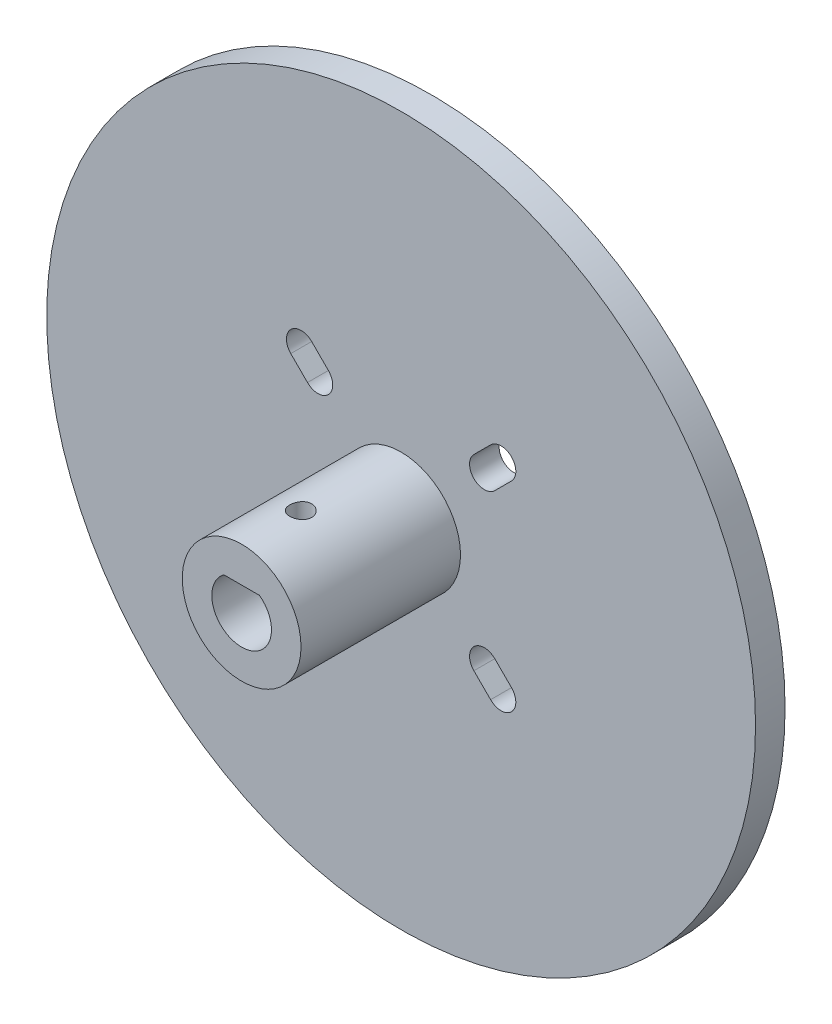
SolidWorks part; units mm, degrees
ref_plane "Front Plane" through (0, 0, 0) normal (0, 0, 1) x (1, 0, 0)
ref_plane "Top Plane" through (0, 0, 0) normal (0, 1, 0) x (1, 0, 0)
ref_plane "Right Plane" through (0, 0, 0) normal (1, 0, 0) x (0, 0, -1)
sketch "Sketch1" plane through (0, 0, 0) normal (0, 0, 1) x (1, 0, 0)
  line L0 (-14.0858, 14.0858) -> (-16.9142, 16.9142) construction
  line L1 (15.5, -15.5) -> (-15.5, -15.5) construction
  line L2 (15.5, -15.5) -> (15.5, 15.5) construction
  line L3 (15.5, 15.5) -> (-15.5, 15.5) construction
  line L4 (-15.5, -15.5) -> (-15.5, 15.5) construction
  line L5 (15.5, -15.5) -> (-15.5, 15.5) construction
  line L6 (15.5, 15.5) -> (-15.5, -15.5) construction
  line L9 (-15.8536, 12.318) -> (-18.682, 15.1464)
  line L10 (-12.318, 15.8536) -> (-15.1464, 18.682)
  line L11 (15.8536, 12.318) -> (18.682, 15.1464)
  line L12 (12.318, 15.8536) -> (15.1464, 18.682)
  line L13 (14.0858, 14.0858) -> (16.9142, 16.9142) construction
  line L14 (12.318, -15.8536) -> (15.1464, -18.682)
  line L15 (15.8536, -12.318) -> (18.682, -15.1464)
  line L16 (14.0858, -14.0858) -> (16.9142, -16.9142) construction
  line L17 (-15.8536, -12.318) -> (-18.682, -15.1464)
  line L18 (-12.318, -15.8536) -> (-15.1464, -18.682)
  line L19 (-14.0858, -14.0858) -> (-16.9142, -16.9142) construction
  circle A0 centre (0, 0) radius 60
  circle A1 centre (-15.5, 15.5) radius 2.1 construction
  circle A2 centre (15.5, 15.5) radius 2.1 construction
  circle A3 centre (15.5, -15.5) radius 2.1 construction
  circle A4 centre (-15.5, -15.5) radius 2.1 construction
  arc A7 (-15.8536, 12.318) -> (-12.318, 15.8536) centre (-14.0858, 14.0858) ccw
  arc A8 (-15.1464, 18.682) -> (-18.682, 15.1464) centre (-16.9142, 16.9142) ccw
  arc A9 (12.318, 15.8536) -> (15.8536, 12.318) centre (14.0858, 14.0858) ccw
  arc A10 (18.682, 15.1464) -> (15.1464, 18.682) centre (16.9142, 16.9142) ccw
  arc A11 (15.8536, -12.318) -> (12.318, -15.8536) centre (14.0858, -14.0858) ccw
  arc A12 (15.1464, -18.682) -> (18.682, -15.1464) centre (16.9142, -16.9142) ccw
  arc A13 (-12.318, -15.8536) -> (-15.8536, -12.318) centre (-14.0858, -14.0858) ccw
  arc A14 (-18.682, -15.1464) -> (-15.1464, -18.682) centre (-16.9142, -16.9142) ccw
  point P16 (-15.5, 15.5)
  point P26 (15.5, 15.5)
  point P33 (15.5, -15.5)
  point P40 (-15.5, -15.5)
  point P45 (0, 0)
  dimension "D1" = 120
  dimension "D3" = 4.2
  dimension "D4" = 2
  dimension "D6" = 2.5
  dimension "D2" = 31
  dimension "D7" = 4
  dimension "D5" = 2
  dimension "D8" = 4
extrude "Boss-Extrude1" add sketch "Sketch1" along normal blind 5
sketch "Sketch2" plane through (0, 0, 5) normal (0, 0, 1) x (1, 0, 0)
  line L0 (-3.0166, 4.05) -> (3.0166, 4.05)
  line L1 (0, 4.05) -> (0, -5.05)
  circle A0 centre (0, 0) radius 5.05
  circle A1 centre (0, 0) radius 10.05
  dimension "D1" = 10.1
  dimension "D2" = 9.1
  dimension "D3" = 5
extrude "Boss-Extrude2" add sketch "Sketch2" along normal blind 27 contours A1 A0 | L0 A0 region at (0, 4.4536, 5) region at (-9.7657, 0, 5)
sketch "Sketch3" plane through (0, 4.05, 0) normal (0, -1, 0) x (-1, 0, 0)
  line L0 (-10.05, -32) -> (10.05, -32) construction
  circle A0 centre (0, -22) radius 1.85
  dimension "D2" = 3.7
  dimension "D1" = 10
extrude "Cut-Extrude1" cut sketch "Sketch3" against normal blind 20 and the other way blind 20
